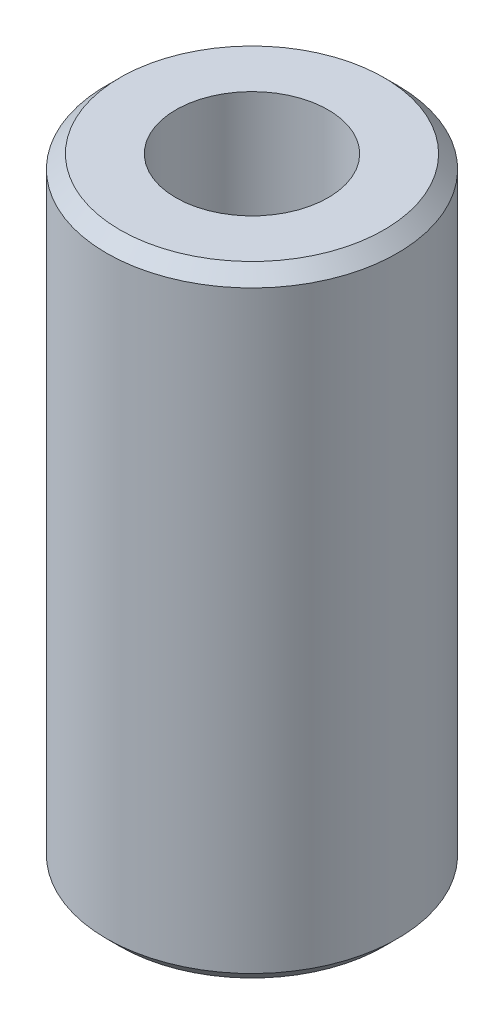
SolidWorks part; units mm, degrees
ref_plane "Front Plane" through (0, 0, 0) normal (0, 0, 1) x (1, 0, 0)
ref_plane "Top Plane" through (0, 0, 0) normal (0, 1, 0) x (1, 0, 0)
ref_plane "Right Plane" through (0, 0, 0) normal (1, 0, 0) x (0, 0, -1)
sketch "Sketch1" plane through (0, 0, 0) normal (0, 1, 0) x (1, 0, 0)
  circle A0 centre (0, 0) radius 47.5
  dimension "SHAFT_OD" = 95
extrude "Boss-Extrude1" add sketch "Sketch1" along normal blind 202.7119
sketch "Sketch2" plane through (0, 0, 0) normal (0, 1, 0) x (1, 0, 0)
  circle A0 centre (0, 0) radius 24.8795
  dimension "BORE_D" = 49.7591
extrude "Cut-Extrude1" cut sketch "Sketch2" along normal through all
chamfer "Chamfer1" distance 4.3887 angle 45 2 edges at (0, 202.7119, 47.5) (0, 0, 47.5)
